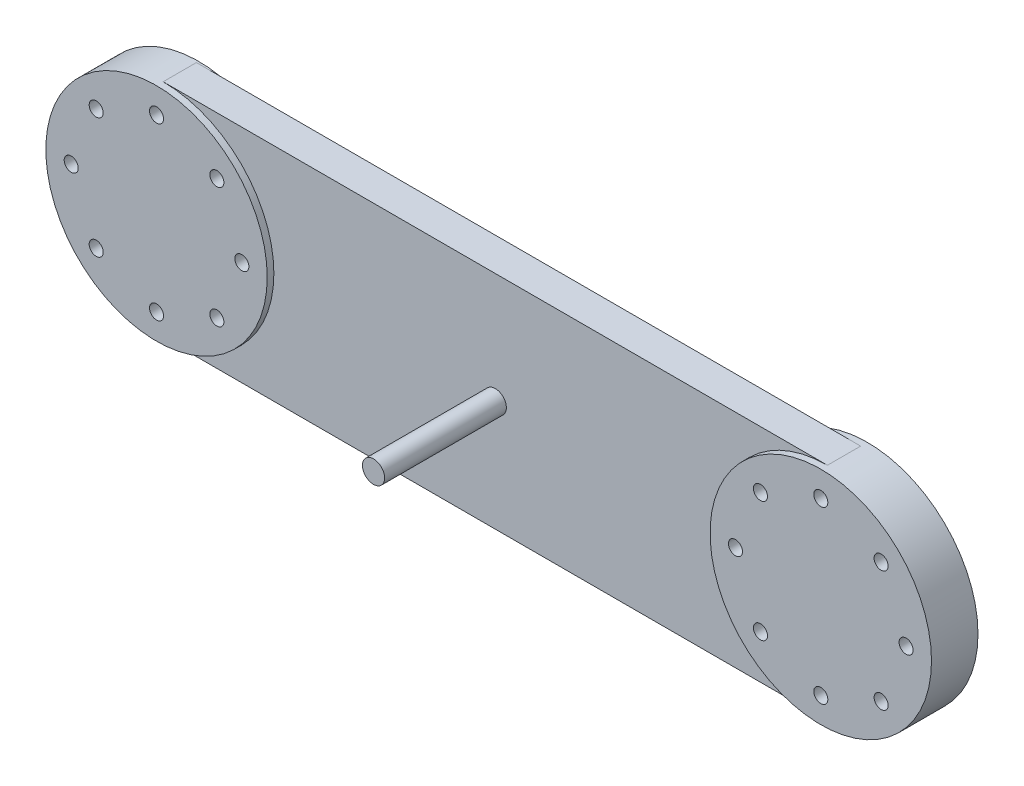
SolidWorks part; units mm, degrees
material "3003 合金"
ref_plane "前视基准面" through (0, 0, 0) normal (0, 0, 1) x (1, 0, 0)
ref_plane "上视基准面" through (0, 0, 0) normal (0, 1, 0) x (1, 0, 0)
ref_plane "右视基准面" through (0, 0, 0) normal (1, 0, 0) x (0, 0, -1)
sketch "草图1" plane through (0, 0, 0) normal (0, 0, 1) x (1, 0, 0)
  line L0 (0, 100) -> (-300, 0) construction
  line L5 (0, 0) -> (-300, 0)
  line L6 (0, 0) -> (0, 100)
  line L7 (0, 100) -> (-300, 100)
  line L8 (-300, 0) -> (-300, 100)
  line L9 (-300, 100) -> (0, 0) construction
  line L10 (-300, 50) -> (-250, 50)
  line L11 (-250, 50) -> (-300, 100) construction
  line L12 (-300, 50) -> (-264.6447, 85.3553) construction
  line L13 (-300, 50) -> (-335.3553, 14.6447)
  line L14 (-150, 50) -> (-150, 0)
  line L15 (-264.6447, 85.3553) -> (-335.3553, 85.3553) construction
  line L16 (-264.6447, 85.3553) -> (-264.6447, 14.6447) construction
  line L17 (-264.6447, 14.6447) -> (-335.3553, 14.6447) construction
  line L18 (-335.3553, 85.3553) -> (-335.3553, 14.6447) construction
  line L19 (-150, 0) -> (-150, 100) construction
  circle A6 centre (0, 50) radius 50
  circle A7 centre (0, 50) radius 25
  circle A8 centre (-300, 50) radius 50
  circle A9 centre (-300, 50) radius 25
  circle A12 centre (-150, 50) radius 5
  circle A13 centre (0, 50) radius 6.5
  circle A14 centre (-261.4697, 50) radius 3.175
  circle A23 centre (-38.5303, 50) radius 3.175
  circle A30 centre (-272.7549, 22.7549) radius 3.175
  circle A31 centre (-300, 11.4697) radius 3.175
  circle A32 centre (-327.2451, 22.7549) radius 3.175
  circle A33 centre (-338.5303, 50) radius 3.175
  circle A34 centre (-327.2451, 77.2451) radius 3.175
  circle A35 centre (-300, 88.5303) radius 3.175
  circle A36 centre (-272.7549, 77.2451) radius 3.175
  circle A37 centre (-27.2451, 77.2451) radius 3.175
  circle A38 centre (-27.2451, 77.2451) radius 3.175
  circle A39 centre (0, 88.5303) radius 3.175
  circle A40 centre (27.2451, 77.2451) radius 3.175
  circle A41 centre (38.5303, 50) radius 3.175
  circle A42 centre (27.2451, 22.7549) radius 3.175
  circle A43 centre (0, 11.4697) radius 3.175
  circle A44 centre (-27.2451, 22.7549) radius 3.175
  point P13 (0, 0)
  point P23 (0, 0)
  point P24 (0, 0)
  point P25 (0, 0)
  point P26 (0, 0)
  point P27 (0, 0)
  point P28 (0, 0)
  point P29 (0, 0)
  point P30 (0, 0)
  point P70 (-300, 50)
  point P87 (0, 50)
  dimension "D1" = 100
  dimension "D2" = 300
  dimension "D3" = 50
  dimension "D4" = 50
  dimension "D5" = 10
  dimension "D6" = 13
  dimension "D7" = 6.35
extrude "凸台-拉伸18" add sketch "草图1" along normal blind 13 contours A8 | A6
extrude "凸台-拉伸21" add sketch "草图1<28>" along normal blind 15 contours L5 L8 L7 L6
sketch "草图1<28>" plane through (0, 0, 0) normal (0, 0, 1) x (1, 0, 0) same geometry as "草图1"
extrude "凸台-拉伸22" add sketch "草图1<30>" along normal blind 70 contours A12
sketch "草图1<30>" plane through (0, 0, 0) normal (0, 0, 1) x (1, 0, 0) same geometry as "草图1"
extrude "切除-拉伸2" cut sketch "草图1<31>" along normal blind 41 contours A8
sketch "草图1<31>" plane through (0, 0, 0) normal (0, 0, 1) x (1, 0, 0) same geometry as "草图1"
extrude "凸台-拉伸23" add sketch "草图1<32>" along normal blind 18 and the other way blind 1 contours A8
sketch "草图1<32>" plane through (0, 0, 0) normal (0, 0, 1) x (1, 0, 0) same geometry as "草图1"
extrude "切除-拉伸3" cut sketch "草图1<33>" along normal blind 242.8 contours A13
sketch "草图1<33>" plane through (0, 0, 0) normal (0, 0, 1) x (1, 0, 0) same geometry as "草图1"
extrude "切除-拉伸5" cut sketch "草图1<35>" against normal blind 69 and the other way blind 130 contours A14
sketch "草图1<35>" plane through (0, 0, 0) normal (0, 0, 1) x (1, 0, 0) same geometry as "草图1"
extrude "切除-拉伸6" cut sketch "草图1<36>" along normal blind 34 contours A6
sketch "草图1<36>" plane through (0, 0, 0) normal (0, 0, 1) x (1, 0, 0) same geometry as "草图1"
extrude "凸台-拉伸24" add sketch "草图1<37>" against normal blind 3 and the other way blind 18 contours A6
sketch "草图1<37>" plane through (0, 0, 0) normal (0, 0, 1) x (1, 0, 0) same geometry as "草图1"
extrude "切除-拉伸7" cut sketch "草图1<41>" along normal blind 87 and the other way blind 98 contours A36 | L8 A35 | L8 A35 | A34 | A33 | L13 A32 | L8 A31 | A30 | L10 A14 | L10 A14 | A44 | A23 | A37 | A39 L6 | A39 L6 | A40 | A42 | A41 | A43 L6 | A43 L6 | A32 | A31 | A43 region at (-1.3475, 11.4697, 0) region at (1.3475, 11.4697, 0) region at (1.3475, 88.5303, 0) region at (-1.3475, 88.5303, 0) region at (-298.6525, 11.4697, 0) region at (-298.6525, 88.5303, 0) region at (-301.3475, 88.5303, 0) region at (-326.2922, 21.8021, 0) region at (-261.4697, 48.6525, 0) region at (-261.4697, 51.3475, 0) region at (-38.5303, 50, 0) region at (-272.7549, 22.7549, 0) region at (-338.5303, 50, 0) region at (-327.2451, 77.2451, 0) region at (-272.7549, 77.2451, 0) region at (-27.2451, 77.2451, 0) region at (27.2451, 77.2451, 0) region at (38.5303, 50, 0) region at (27.2451, 22.7549, 0) region at (-27.2451, 22.7549, 0)
sketch "草图1<41>" plane through (0, 0, 0) normal (0, 0, 1) x (1, 0, 0) same geometry as "草图1"
